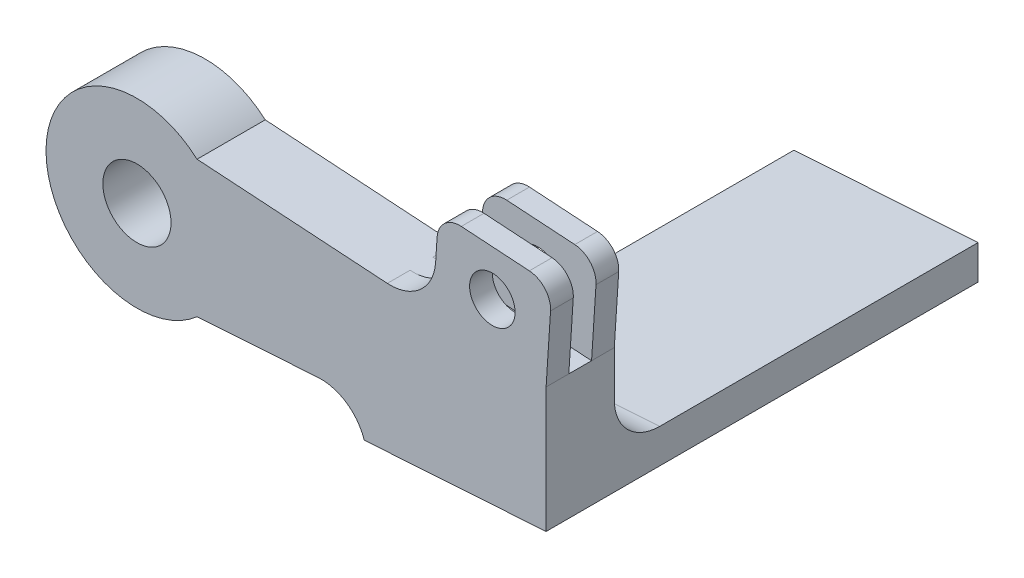
SolidWorks part; units mm, degrees
ref_plane "Front Plane" through (0, 0, 0) normal (0, 0, 1) x (1, 0, 0)
ref_plane "Top Plane" through (0, 0, 0) normal (0, 1, 0) x (1, 0, 0)
ref_plane "Right Plane" through (0, 0, 0) normal (1, 0, 0) x (0, 0, -1)
sketch "Sketch1" plane through (0, 0, 0) normal (0, 0, 1) x (1, 0, 0)
  circle A0 centre (0, 0) radius 7.5
  circle A1 centre (0, 0) radius 20
  dimension "D1" = 15
  dimension "D2" = 40
extrude "Boss-Extrude1" add sketch "Sketch1" along normal mid plane 15
sketch "Sketch2" plane through (0, 0, 0) normal (0, 0, 1) x (1, 0, 0)
  line L0 (20, 0) -> (90, 0) construction
  line L1 (13.2288, 15) -> (13.2288, -15) construction
  line L2 (13.2288, 15) -> (90, 10)
  line L3 (13.2288, -15) -> (90, -10)
  line L4 (90, -10) -> (90, 10)
  circle A0 centre (0, 0) radius 20 construction
  arc A1 (13.2288, 15) -> (13.2288, -15) centre (0, 0) cw
  point P18 (90, 0)
  dimension "D1" = 90
  dimension "D2" = 30
  dimension "D3" = 20
extrude "Boss-Extrude2" add sketch "Sketch2" along normal mid plane 15
sketch "Sketch4" plane through (1.0287, 15.7946, 0) normal (0.065, 0.9979, 0) x (0.9979, -0.065, 0)
  line L0 (0, 0) -> (89.1598, 0) construction
  line L1 (89.1598, -7.5) -> (89.1598, 7.5) construction
  line L2 (89.1598, 7.5) -> (12.2259, 7.5) construction
  line L3 (64.1598, -7.5) -> (89.1598, -7.5)
  line L4 (64.1598, -7.5) -> (64.1598, 7.5)
  line L5 (64.1598, 7.5) -> (89.1598, 7.5)
  line L6 (89.1598, -7.5) -> (89.1598, 7.5)
  line L7 (64.1598, -7.5) -> (89.1598, 7.5) construction
  line L8 (64.1598, 7.5) -> (89.1598, -7.5) construction
  line L9 (64.1598, 2.5) -> (89.1598, 2.5)
  line L10 (64.1598, -2.5) -> (89.1598, -2.5)
  line L11 (76.6598, 2.5) -> (76.6598, 0) construction
  line L12 (76.6598, 0) -> (76.6598, -2.5) construction
  point P5 (76.6598, 0)
  line M7 (89.1598, 7.5) -> (12.2259, 7.5)
  line M9 (12.2259, -7.5) -> (89.1598, -7.5)
  line M10 (89.1598, -7.5) -> (89.1598, 7.5)
  dimension "D1" = 25
  dimension "D2" = 5
extrude "Boss-Extrude3" add sketch "Sketch4" along normal blind 20 contours L4 L9 L6 M7 | L10 L4 M9 M10 region at (77.5264, 10.8124, 5) region at (77.5264, 10.8124, -5)
sketch "Sketch5" plane through (0, 0, 7.5) normal (0, 0, 1) x (1, 0, 0)
  line L0 (65.0529, 11.6248) -> (91.2998, 29.9577) construction
  circle A0 centre (78.1763, 20.7912) radius 5
  dimension "D1" = 10
extrude "Cut-Extrude1" cut sketch "Sketch5" against normal through all
fillet "Fillet1" radius 5 4 edges at (66.3527, 31.5825, 5) (91.2998, 29.9577, 5) (91.2998, 29.9577, -5) (66.3527, 31.5825, -5)
fillet "Fillet2" radius 10 2 edges at (65.0529, 11.6248, 5) (65.0529, 11.6248, -5)
sketch "Sketch6" plane through (0, 0, -7.5) normal (0, 0, -1) x (-1, 0, 0)
  line L6 (-90, -10) -> (-90, -17.5318)
  line L7 (-90, -17.5318) -> (-50, -20.137)
  line L8 (-50, -20.137) -> (-49.5115, -12.637)
  line L9 (-13.2288, -15) -> (-90, -10) construction
  line L10 (-49.5115, -12.637) -> (-90, -10)
  point P2 (-66.8336, -18.9934)
  dimension "D1" = 40
  dimension "D2" = 7.5
extrude "Boss-Extrude4" add sketch "Sketch6" against normal up to surface (15 mm away) and the other way blind 80 up to face at (83.1763, 20.7912, 7.5)
fillet "Fillet3" radius 10 1 edges at (49.5115, -12.637, 0)
fillet "Fillet4" radius 10 1 edges at (69.7558, -11.3185, -7.5)
